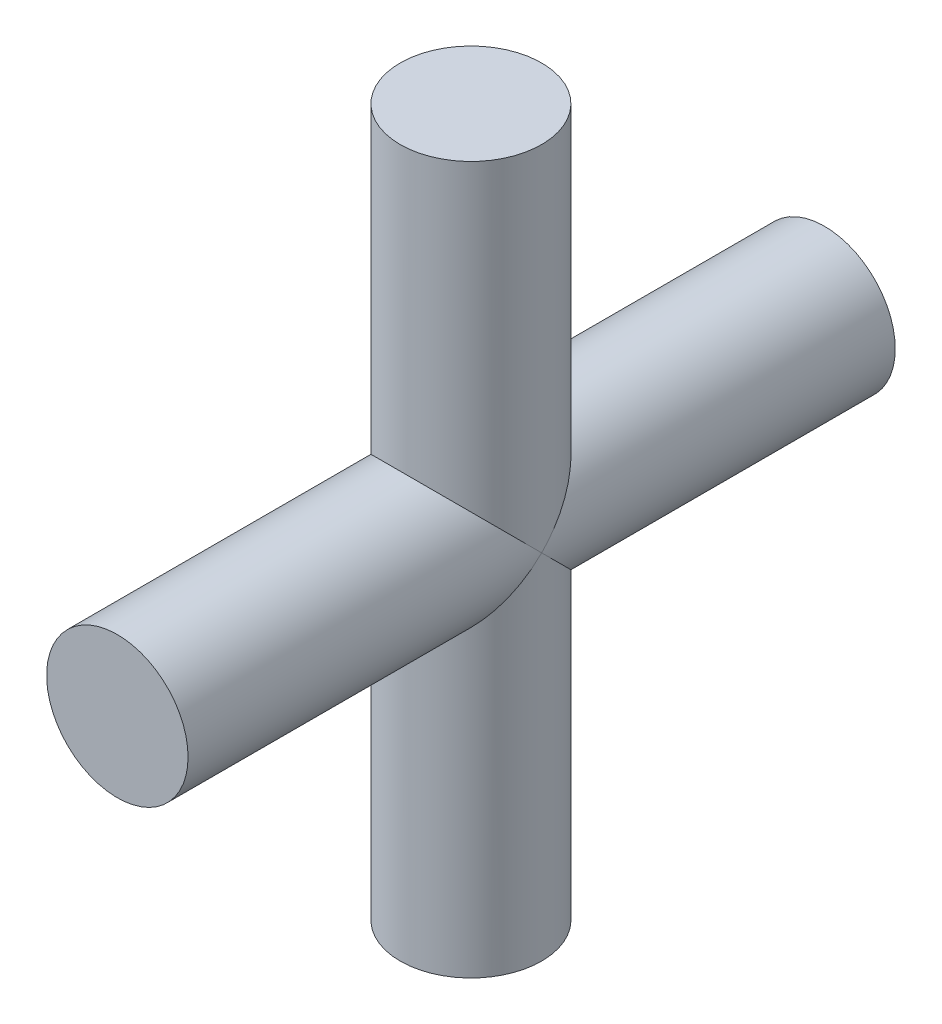
SolidWorks part; units mm, degrees
ref_plane "Front Plane" through (0, 0, 0) normal (0, 0, 1) x (1, 0, 0)
ref_plane "Top Plane" through (0, 0, 0) normal (0, 1, 0) x (1, 0, 0)
ref_plane "Right Plane" through (0, 0, 0) normal (1, 0, 0) x (0, 0, -1)
sketch "Sketch1" plane through (0, 0, 0) normal (0, 0, 1) x (1, 0, 0)
  circle A0 centre (0, 0) radius 5
  dimension "D1" = 10
extrude "Boss-Extrude1" add sketch "Sketch1" along normal blind 50
sketch "Sketch2" plane through (0, 0, 0) normal (0, 1, 0) x (1, 0, 0)
  circle A0 centre (0, -25) radius 5
  dimension "D2" = 10
extrude "Boss-Extrude2" add sketch "Sketch2" along normal blind 25 and the other way blind 25
